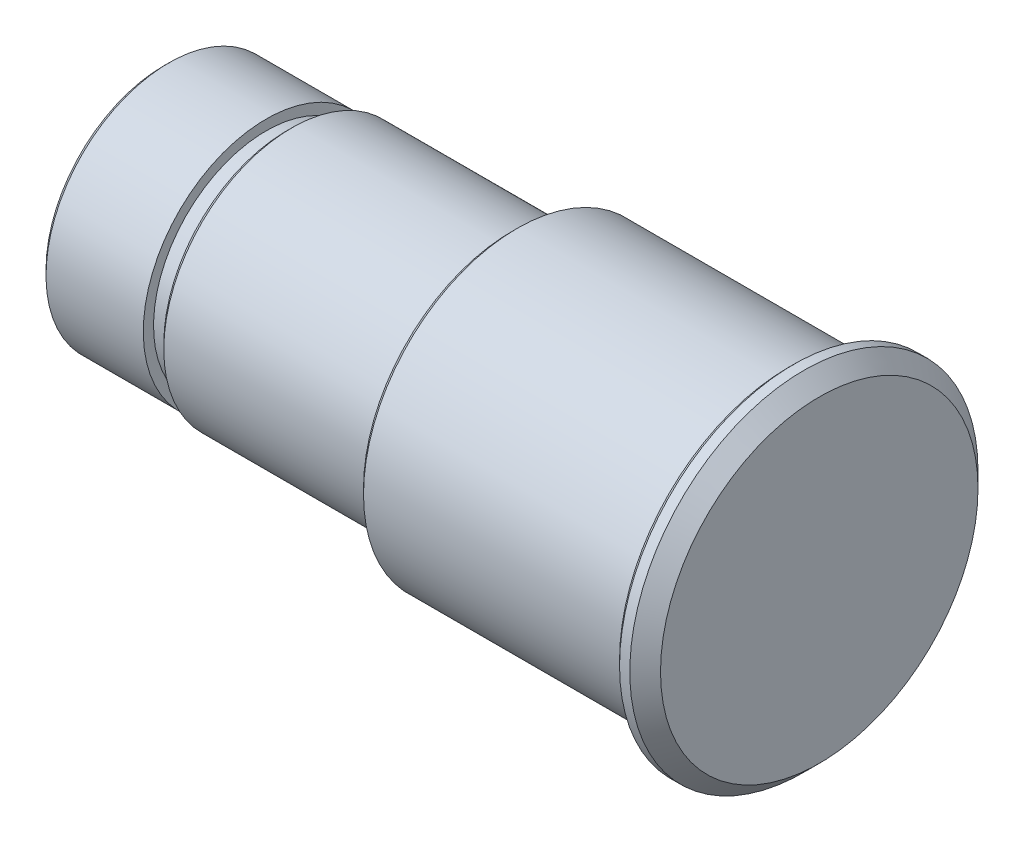
SolidWorks part; units mm, degrees
ref_plane "前视基准面" through (0, 0, 0) normal (0, 0, 1) x (1, 0, 0)
ref_plane "上视基准面" through (0, 0, 0) normal (0, 1, 0) x (1, 0, 0)
ref_plane "右视基准面" through (0, 0, 0) normal (1, 0, 0) x (0, 0, -1)
other "Configuration Table"
sketch "草图1" plane through (0, 0, 0) normal (0, 0, 1) x (1, 0, 0)
  line L0 (0, 0) -> (0, 12)
  line L1 (0, 12) -> (10, 12)
  line L2 (10, 12) -> (10, 11)
  line L3 (10, 11) -> (12, 11)
  line L4 (12, 11) -> (12, 12.5)
  line L5 (12, 12.5) -> (34, 12.5)
  line L6 (34, 12.5) -> (34, 15)
  line L7 (34, 15) -> (61, 15)
  line L8 (61, 15) -> (61, 17)
  line L9 (61, 17) -> (64, 17)
  line L10 (64, 17) -> (64, 0)
  line L11 (64, 0) -> (0, 0)
  line L12 (0, 0) -> (-13.0739, 0) construction
  dimension "D1" = 24
  dimension "D2" = 25
  dimension "D3" = 30
  dimension "D4" = 34
  dimension "D5" = 12
  dimension "D6" = 27
  dimension "D7" = 3
  dimension "D8" = 52
  dimension "D9" = 2
  dimension "D10" = 1
revolve "旋转1" add sketch "草图1" angle 360 about L12
chamfer "倒角1" distance 1.5 angle 45 1 edges at (64, 0, -17)
chamfer "倒角2" distance 0.5 angle 45 5 edges at (34, 0, -15) (34, 0, -12.5) (61, 0, -17) (12, 0, -12.5) (0, 0, -12)
ref_plane "基准面1" through (0, -9, 0) normal (0, 1, 0) x (1, 0, 0)
sketch "草图3" plane through (0, -9, 0) normal (0, 1, 0) x (1, 0, 0)
  line L0 (0, 2.5) -> (9.5, 2.5)
  line L1 (0, 11.5) -> (0, -11.5) construction
  line L2 (9.5, -2.5) -> (0, -2.5)
  line L3 (0, -2.5) -> (0, 2.5)
  line L4 (12, 11) -> (12, -11) construction
  arc A0 (9.5, 2.5) -> (9.5, -2.5) centre (9.5, 0) cw
  point P6 (5.3439, 0.2691)
  point P8 (0, 0)
  dimension "D1" = 5
extrude "切除-拉伸1" cut sketch "草图3" against normal up to next
